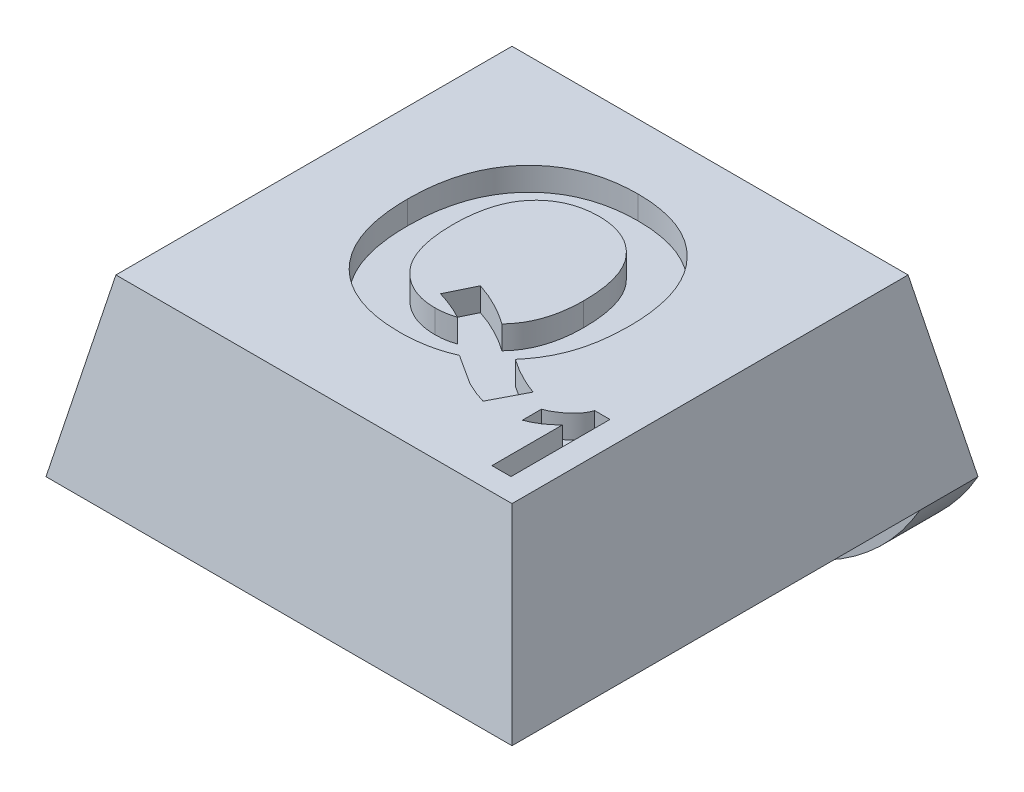
SolidWorks part; units mm, degrees
ref_plane "Front Plane" through (0, 0, 0) normal (0, 0, 1) x (1, 0, 0)
ref_plane "Top Plane" through (0, 0, 0) normal (0, 1, 0) x (1, 0, 0)
ref_plane "Right Plane" through (0, 0, 0) normal (1, 0, 0) x (0, 0, -1)
sketch "Sketch1" plane through (0, 0, 0) normal (0, 1, 0) x (1, 0, 0)
  line L1 (0, 0) -> (8, 0)
  line L2 (0, 0) -> (0, 8)
  line L3 (0, 8) -> (8, 8)
  line L4 (8, 0) -> (8, 8)
  dimension "D1" = 8
  dimension "D2" = 8
extrude "Boss-Extrude1" add sketch "Sketch1" along normal blind 3
sketch "Sketch2" plane through (0, 0, 0) normal (0, 0, 1) x (1, 0, 0)
  line L0 (0, 0) -> (0.6, 3)
  line L1 (0, 3) -> (8, 3) construction
  line L2 (0.6, 3) -> (0, 3)
  line L3 (0, 3) -> (0, 0)
  line L4 (8, 0) -> (7.4, 3)
  line L5 (7.4, 3) -> (8, 3)
  line L6 (8, 3) -> (8, 0)
  dimension "D1" = 0.6
  dimension "D2" = 0.6
extrude "Cut-Extrude1" cut sketch "Sketch2" against normal through all both and the other way through all
sketch "Sketch3" plane through (0, 0, 0) normal (1, 0, 0) x (0, 0, -1)
  line L0 (0, 0) -> (0.6, 3)
  line L1 (8, 3) -> (0, 3) construction
  line L2 (0.6, 3) -> (0, 3)
  line L3 (0, 3) -> (0, 0)
  line L4 (8, 3) -> (7.4, 3)
  line L5 (7.4, 3) -> (8, 0)
  line L6 (8, 3) -> (8, 0)
  dimension "D1" = 0.6
  dimension "D2" = 0.6
extrude "Cut-Extrude2" cut sketch "Sketch3" along normal blind 11
sketch "Sketch4" plane through (0, 0, 0) normal (0, -1, 0) x (1, 0, 0)
  line L0 (8, 0) -> (8, -8) construction
  line L3 (0, 0) -> (8, 0) construction
  circle A0 centre (4, -3.75) radius 1.8
  dimension "D1" = 3.6
  dimension "D2" = 4
  dimension "D3" = 3.75
extrude "Cut-Extrude3" cut sketch "Sketch4" against normal blind 0.8
sketch "Sketch5" plane through (0, 0, 0) normal (0, -1, 0) x (1, 0, 0)
  line L0 (8, 0) -> (8, -8) construction
  line L1 (0, -8) -> (8, -8)
  line L2 (0, -8) -> (0, -7)
  line L3 (0, -7) -> (8, -7)
  line L4 (8, -8) -> (8, -7)
  dimension "D1" = 1
extrude "Boss-Extrude2" add sketch "Sketch5" along normal blind 2
fillet "Fillet1" radius 4 2 edges at (8, -2, -7.5) (0, -2, -7.5)
sketch "Sketch6" plane through (0, 3, 0) normal (0, 1, 0) x (1, 0, 0)
  text T0 "Q" font "Arial" height 4
extrude "Cut-Extrude4" cut sketch "Sketch6" against normal blind 0.4
sketch "Sketch7" plane through (0, 3, 0) normal (0, 1, 0) x (1, 0, 0)
  text T0 "1" font "Arial" height 1.7
extrude "Cut-Extrude5" cut sketch "Sketch7" against normal blind 0.4
